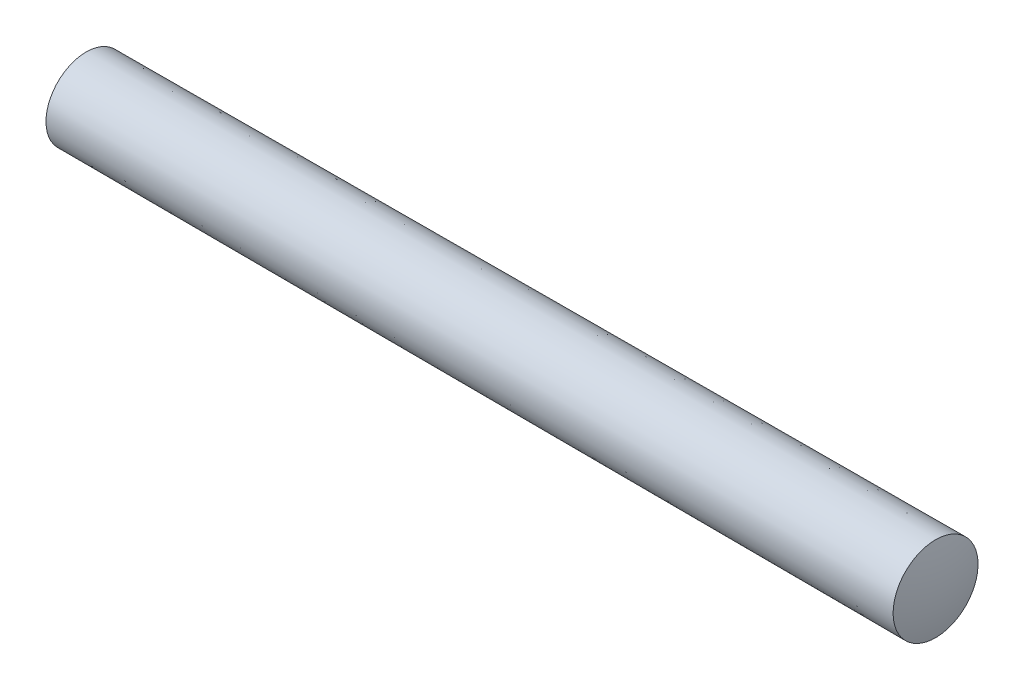
SolidWorks part; units mm, degrees
ref_plane "Front Plane" through (0, 0, 0) normal (0, 0, 1) x (1, 0, 0)
ref_plane "Top Plane" through (0, 0, 0) normal (0, 1, 0) x (1, 0, 0)
ref_plane "Right Plane" through (0, 0, 0) normal (1, 0, 0) x (0, 0, -1)
sketch "BodySke" plane through (0, 0, 0) normal (0, 0, 1) x (1, 0, 0)
  line L0 (-103.4174, 0) -> (209.4275, 0) construction
  line L1 (-0.3618, 0) -> (63.9033, 0)
  line L2 (0, 3.0096) -> (63.5, 3.175)
  line L3 (3.4925, 0) -> (-3.4925, 0) construction
  line L4 (0, 3.0096) -> (0, 0) construction
  line L5 (0, -3.4925) -> (0, 3.4925) construction
  arc A0 (0, 3.0096) -> (-0.3618, 0) centre (12.3382, 0) ccw
  arc A1 (63.5, 3.175) -> (63.9033, 0) centre (51.2033, 0) cw
  dimension "D4" = 12.7
  dimension "D5" = 12.7
  dimension "Diameter" = 6.35
  dimension "D2" = 6.0193
  dimension "Length" = 63.5
revolve "BaseBody" add sketch "BodySke" angle 360 about L0
equation "\"D4@BodySke\" = \"Diameter@BodySke\"*2"
equation "\"D5@BodySke\" = \"Diameter@BodySke\" * 2"
equation "\"D2@BodySke\" = \"Diameter@BodySke\"-\"Diameter@BodySke\" * \"Length@BodySke\" / 48"
